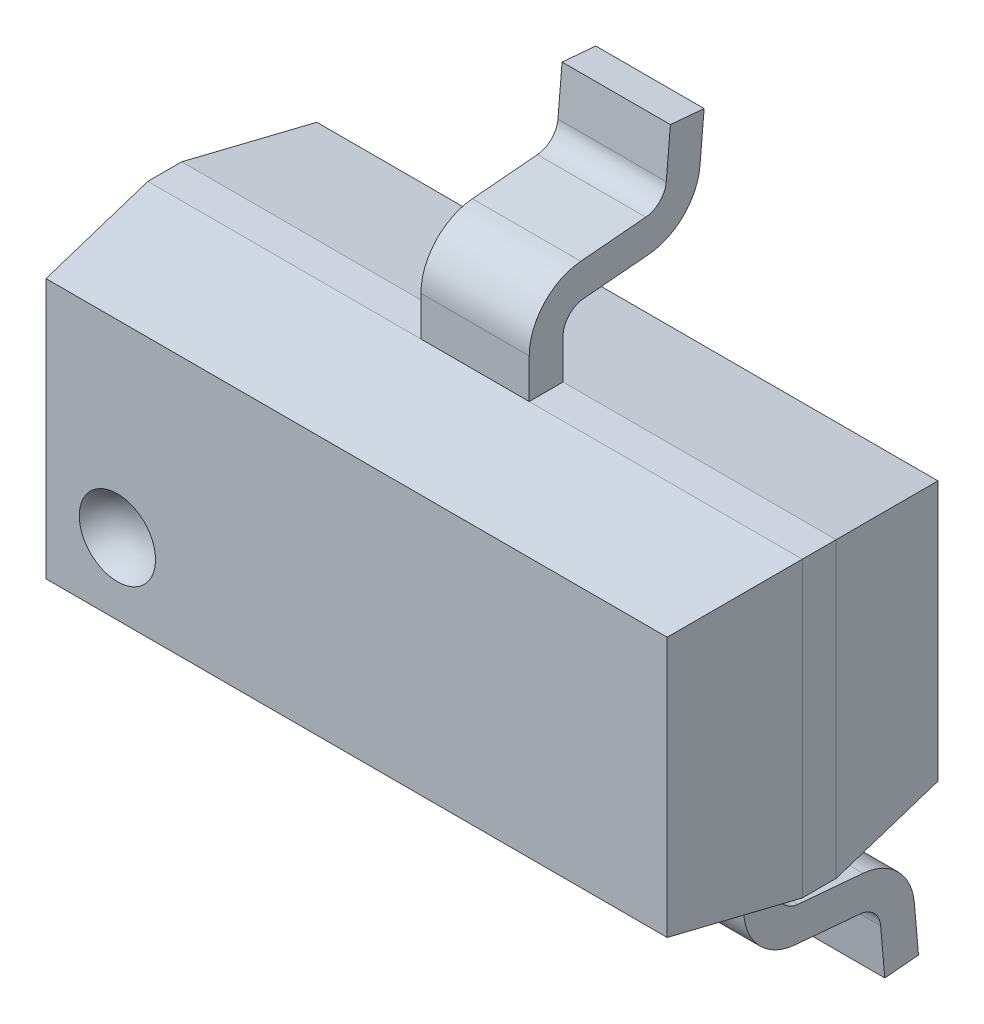
SolidWorks part; units mm, degrees
ref_plane "Top Plane" through (0, 0, 0) normal (0, 0, 1) x (1, 0, 0)
ref_plane "Front Plane" through (0, 0, 0) normal (0, 1, 0) x (1, 0, 0)
ref_plane "Right Plane" through (0, 0, 0) normal (1, 0, 0) x (0, 0, -1)
ref_axis "CenterAxis" through (0, 0, -0.0875) along (0, 0, 1)
ref_plane "Pin1Plane" through (-1.19, 0, 0) normal (1, 0, 0) x (0, 0, -1)
sketch "BodyWxH" plane through (0, 0, 0) normal (1, 0, 0) x (0, 0, -1)
  line L0 (0, 1.54) -> (0, -1.54) construction
  line L1 (-1.3, 0.65) -> (-0.1, 0.65)
  line L2 (-1.3, 0.65) -> (-1.3, -0.65)
  line L3 (-1.3, -0.65) -> (-0.1, -0.65)
  line L4 (-0.1, 0.65) -> (-0.1, -0.65)
  line L6 (-1.3, 0) -> (-0.1, 0) construction
  line L7 (0.0875, 0) -> (-1.8375, 0) construction
  dimension "W" = 1.3
  dimension "SO" = 0.1
  dimension "HMax" = 1.3
extrude "Boss-Body" add sketch "BodyWxH" along normal mid plane 2.9
chamfer "Chamfer1" distance 0.525 angle 8 8 edges at (0, -0.65, 0.1) (1.45, 0, 0.1) (0, 0.65, 0.1) (-1.45, 0, 0.1) (0, 0.65, 1.3) (1.45, 0, 1.3) (0, -0.65, 1.3) (-1.45, 0, 1.3) first distance on face at (0, -0.65, 0.7) first distance on face at (1.45, 0, 0.7) first distance on face at (0, 0.65, 0.7) first distance on face at (-1.45, 0, 0.7)
sketch "LeadCross" plane through (-1.19, 0, 0) normal (1, 0, 0) x (0, 0, -1)
  line L0 (0, -1.3869) -> (-0.1494, -1.4)
  line L1 (-0.1494, -1.4) -> (-0.1678, -1.1903)
  line L2 (-0.2587, -1.0994) -> (-0.5468, -1.0742)
  line L3 (-0.775, -0.8252) -> (-0.775, 0.8252)
  line L4 (-0.5468, 1.0742) -> (-0.2587, 1.0994)
  line L5 (-0.1678, 1.1903) -> (-0.1494, 1.4)
  line L6 (-0.1494, 1.4) -> (0, 1.3869)
  line L7 (0, 1.3869) -> (-0.0183, 1.1773)
  line L8 (-0.2456, 0.95) -> (-0.5337, 0.9248)
  line L9 (-0.625, 0.8252) -> (-0.625, -0.8252)
  line L10 (-0.5337, -0.9248) -> (-0.2456, -0.95)
  line L11 (-0.0183, -1.1773) -> (0, -1.3869)
  line L12 (0, 1.54) -> (0, -1.54) construction
  line L13 (-0.7, 0) -> (0, 0) construction
  line L14 (0.9625, 0) -> (-0.9625, 0) construction
  line L15 (-0.7, 0.6632) -> (-0.7, -0.6632) construction
  arc A0 (-0.0183, 1.1773) -> (-0.2456, 0.95) centre (-0.2674, 1.199) cw
  arc A1 (-0.2587, 1.0994) -> (-0.1678, 1.1903) centre (-0.2674, 1.199) ccw
  arc A2 (-0.2456, -0.95) -> (-0.0183, -1.1773) centre (-0.2674, -1.199) cw
  arc A3 (-0.1678, -1.1903) -> (-0.2587, -1.0994) centre (-0.2674, -1.199) ccw
  arc A4 (-0.625, -0.8252) -> (-0.5337, -0.9248) centre (-0.525, -0.8252) ccw
  arc A5 (-0.5468, -1.0742) -> (-0.775, -0.8252) centre (-0.525, -0.8252) cw
  arc A6 (-0.775, 0.8252) -> (-0.5468, 1.0742) centre (-0.525, 0.8252) cw
  arc A7 (-0.5337, 0.9248) -> (-0.625, 0.8252) centre (-0.525, 0.8252) ccw
  dimension "BendRadius" = 0.1
  dimension "LeadThickness" = 0.15
  dimension "D2" = 5
  dimension "ToeLength" = 0.45
  dimension "D4" = 85
  dimension "MidPlane" = 0.7
  dimension "LeadSpan" = 2.8
extrude "Pins" add sketch "LeadCross" along normal blind 0.48
pattern_linear "PatternLeads" count 3 along (1, 0, 0) of "Pins"
ref_plane "Pin1MarkPlane" through (-1.06, 0, 0) normal (1, 0, 0) x (0, 0, -1)
sketch "Pin1Indent" plane through (-1.06, 0, 0) normal (1, 0, 0) x (0, 0, -1)
  line L0 (-1.3975, -0.065) -> (-1.3975, -0.455) construction
  line L1 (0, 1.54) -> (0, -1.54) construction
  line L2 (-1.3975, -0.26) -> (-1.2025, -0.26) construction
  line L3 (0.9625, 0) -> (-0.9625, 0) construction
  line L4 (-1.3975, -0.065) -> (-1.3975, -0.455)
  arc A1 (-1.3975, -0.455) -> (-1.3975, -0.065) centre (-1.3975, -0.26) ccw
  dimension "CutHeight" = 1.3975
  dimension "CutSize" = 0.39
  dimension "CutOffset" = 0.26
revolve "Cut-Pin1Indent" cut sketch "Pin1Indent" angle 360 mid plane about L4
other "DeleteFace1" face at (0, -1.1366, 0.205) face at (0, -1.2952, 0.1586) face at (0, -1.0868, 0.4027) face at (-0.24, -1.0131, 0.3942) face at (0.24, -1.0131, 0.3942) face at (0, -0.9719, 0.6851) face at (0, -0.7376, 0.775) face at (0, -1.2821, 0.0092) face at (0, -1.043, 0.1113) face at (0, -1.3935, 0.0747) face at (0, -0.8839, 0.589) face at (0, -0.7376, 0.625) face at (0, -0.9374, 0.3897) face at (0.95, 0.9719, 0.6851) face at (0.95, 0.7376, 0.775) face at (0.71, 1.0131, 0.3942) face at (1.19, 1.0131, 0.3942) face at (0.95, 1.0868, 0.4027) face at (0.95, 1.2952, 0.1586) face at (0.95, 1.1366, 0.205) face at (0.95, 1.3935, 0.0747) face at (0.95, 0.8839, 0.589) face at (0.95, 0.9374, 0.3897) face at (0.95, 0.7376, 0.625) face at (0.95, 1.043, 0.1113) face at (0.95, 1.2821, 0.0092) face at (-0.71, 1.0131, 0.3942) face at (-0.95, 0.7376, 0.625) face at (-0.95, 0.8839, 0.589) face at (-0.95, 0.9374, 0.3897) face at (-0.95, 1.043, 0.1113) face at (-0.95, 1.2821, 0.0092) face at (-0.95, 1.3935, 0.0747) face at (-0.95, 1.2952, 0.1586) face at (-0.95, 1.1366, 0.205) face at (-0.95, 1.0868, 0.4027) face at (-0.95, 0.9719, 0.6851) face at (-0.95, 0.7376, 0.775) face at (-1.19, 1.0131, 0.3942) and patch yes
equation "\"D1@Chamfer1\" = (\"HMax@BodyWxH\"-\"SO@BodyWxH\"-\"LeadThickness@LeadCross\")/2"
equation "\"D1@Pin1Plane\" = (\"D1@PatternLeads\"-1)*\"LeadPitch@PatternLeads\"/2+(\"LeadWidth@Pins\"/2) ' 1st pin edge plane"
equation "\"CutSize@Pin1Indent\" = \"W@BodyWxH\"*0.3 ' Dent radius is half this value"
equation "\"CutOffset@Pin1Indent\" = \"W@BodyWxH\"/2-(\"W@BodyWxH\"*0.3) ' Dent distance from the center line"
equation "\"D1@Pin1MarkPlane\" = \"D1@Boss-Body\"/2-(\"W@BodyWxH\"*0.3) ' Pin 1 dent lies along this plane"
equation "\"CutHeight@Pin1Indent\" = \"HMax@BodyWxH\"+(\"CutSize@Pin1Indent\"/4) ' Dent is cut by sphere this high"
equation "\"MidPlane@LeadCross\" = (\"HMax@BodyWxH\"+\"SO@BodyWxH\")/2"
